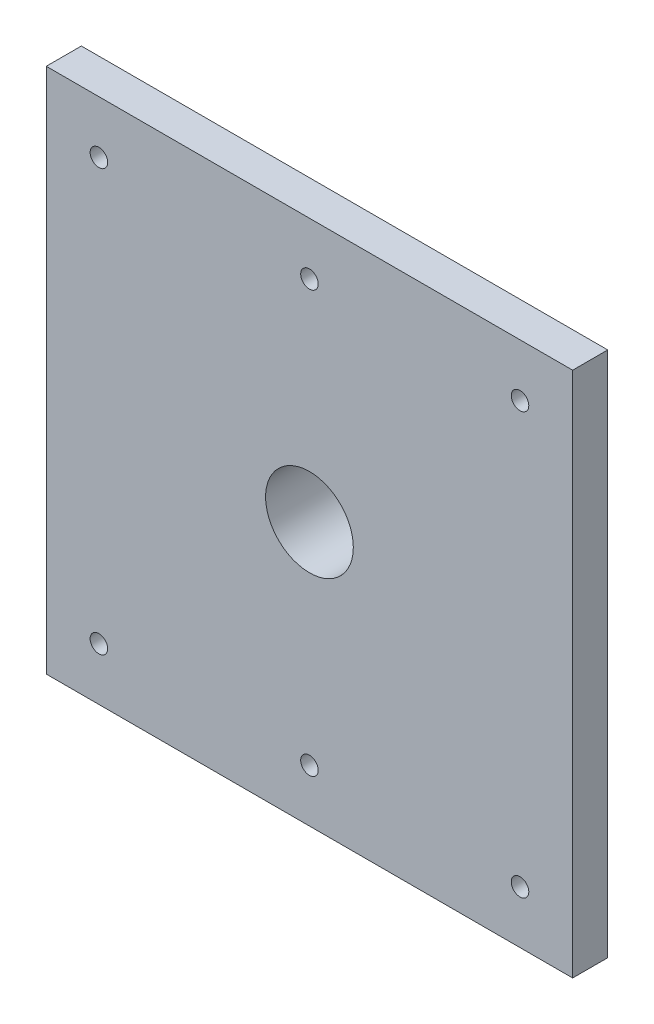
SolidWorks part; units mm, degrees
ref_plane "前视基准面" through (0, 0, 0) normal (0, 0, 1) x (1, 0, 0)
ref_plane "上视基准面" through (0, 0, 0) normal (0, 1, 0) x (1, 0, 0)
ref_plane "右视基准面" through (0, 0, 0) normal (1, 0, 0) x (0, 0, -1)
sketch "草图1" plane through (0, 0, 0) normal (0, 0, 1) x (1, 0, 0)
  line L1 (75, 75) -> (-75, 75)
  line L2 (75, 75) -> (75, -75)
  line L3 (75, -75) -> (-75, -75)
  line L4 (-75, 75) -> (-75, -75)
  line L5 (0, -75) -> (0, 75) construction
  line L6 (75, 0) -> (-75, 0) construction
  circle A0 centre (0, 0) radius 12.5
  point P0 (0, 0)
  dimension "D1" = 150
  dimension "D2" = 150
extrude "拉伸-薄壁1" add sketch "草图1" against normal blind 15 thin contours A0 thin type one direction wall 2
extrude "凸台-拉伸1" add sketch "草图1<3>" along normal blind 10
sketch "草图1<3>" plane through (0, 0, 0) normal (0, 0, 1) x (1, 0, 0) same geometry as "草图1"
sketch "草图2" plane through (0, 0, 10) normal (0, 0, 1) x (1, 0, 0)
  line L8 (60, 60) -> (-60, 60)
  line L9 (-60, 60) -> (-60, -60)
  line L10 (-60, -60) -> (60, -60)
  line L11 (60, -60) -> (60, 60)
  line L12 (60, 60) -> (-60, 60) construction
  line L13 (-60, 60) -> (-60, -60) construction
  line L14 (-60, -60) -> (60, -60) construction
  line L15 (60, -60) -> (60, 60) construction
  circle A0 centre (-60, 60) radius 2.5
  circle A1 centre (0, 60) radius 2.5
  circle A2 centre (60, 60) radius 2.5
  circle A3 centre (60, -60) radius 2.5
  circle A4 centre (0, -60) radius 2.5
  circle A5 centre (-60, -60) radius 2.5
  dimension "D1" = 15
extrude "切除-拉伸1" cut sketch "草图2" against normal blind 10
